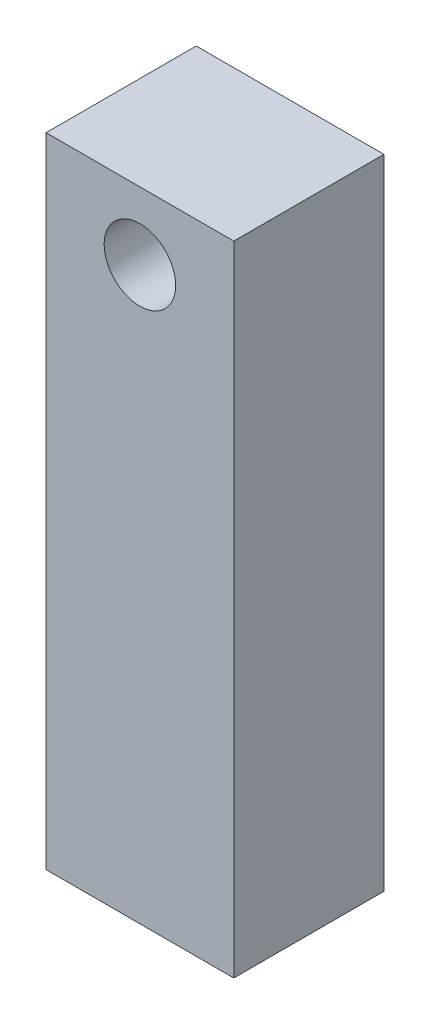
SolidWorks part; units mm, degrees
material "Plain Carbon Steel"
ref_plane "Front Plane" through (0, 0, 0) normal (0, 0, 1) x (1, 0, 0)
ref_plane "Top Plane" through (0, 0, 0) normal (0, 1, 0) x (1, 0, 0)
ref_plane "Right Plane" through (0, 0, 0) normal (1, 0, 0) x (0, 0, -1)
sketch "Sketch1" plane through (0, 0, 0) normal (0, 1, 0) x (1, 0, 0)
  line L0 (-12.5, -10) -> (12.5, -10)
  line L1 (12.5, -10) -> (12.5, 10)
  line L2 (12.5, 10) -> (-12.5, 10)
  line L3 (-12.5, 10) -> (-12.5, -10)
  dimension "D1" = 25
  dimension "D2" = 20
  dimension "D3" = 12.5
  dimension "D4" = 10
extrude "Boss-Extrude1" add sketch "Sketch1" along normal blind 85
sketch "Sketch2" plane through (0, 0, 0) normal (0, 0, 1) x (1, 0, 0)
  circle A0 centre (0, 76) radius 4.7625
  dimension "D2" = 9.525
  dimension "D1" = 76
extrude "Cut-Extrude1" cut sketch "Sketch2" against normal mid plane 24
ref_plane "Plane1" through (0, 76, 0) normal (0, 1, 0) x (1, 0, 0)
ref_axis "Axis1" through (0, 76, -11) along (0, 0, 1)
